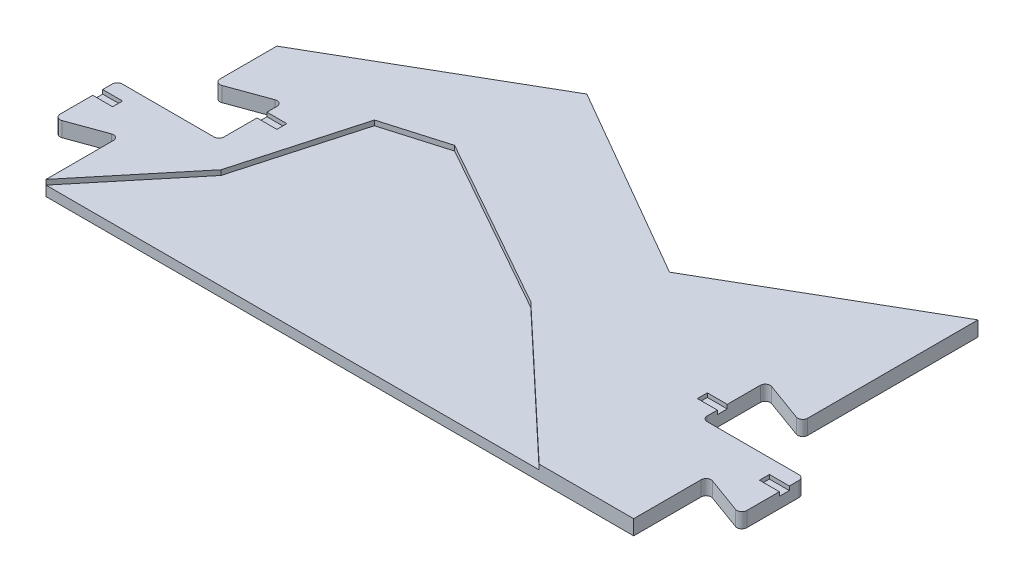
SolidWorks part; units mm, degrees
ref_plane "Přední rovina" through (0, 0, 0) normal (0, 0, 1) x (1, 0, 0)
ref_plane "Horní rovina" through (0, 0, 0) normal (0, 1, 0) x (1, 0, 0)
ref_plane "Pravá rovina" through (0, 0, 0) normal (1, 0, 0) x (0, 0, -1)
sketch "Skica1" plane through (0, 0, 0) normal (0, 1, 0) x (1, 0, 0)
  line L0 (-118.1438, 0) -> (-118.1438, 15)
  line L1 (-118.1438, 15) -> (-128.0938, 11.3785)
  line L2 (-128.0938, 11.3785) -> (-128.0938, 24.2785)
  line L3 (-107.6438, 24.2785) -> (-107.6438, 37.3785)
  line L4 (-107.6438, 37.3785) -> (-118.1432, 33.557)
  line L5 (-118.1432, 33.557) -> (-118.1432, 46.4149)
  line L6 (-118.1432, 46.4149) -> (-78.6351, 69.2249)
  line L7 (-78.6351, 69.2249) -> (-39.3176, 46.5249)
  line L8 (-118.1438, 15) -> (-118.1438, 58.9257) construction
  line L9 (-107.6438, 24.2785) -> (-128.0938, 24.2785)
  line L10 (-118.1438, 0) -> (-102.2271, 19.2785)
  line L11 (-102.2271, 19.2785) -> (-95.473, 43.3489)
  line L12 (-95.473, 43.3489) -> (-82.9972, 47.0032)
  line L13 (-82.9972, 47.0032) -> (-48.113, 27.4305)
  line L14 (-39.3176, 46.5249) -> (0, 69.2249)
  line L15 (-118.1438, 0) -> (0, 0)
  line L16 (-48.113, 27.4305) -> (-19, 0)
  line L17 (0, 0) -> (0, 15)
  line L18 (0, 69.2249) -> (0, 0) construction
  line L19 (-10.5, 24.2783) -> (9.9505, 24.2783)
  line L20 (0, 69.2249) -> (0, 33.5566)
  line L21 (0, 15) -> (9.9505, 11.3783)
  line L22 (9.9505, 24.2783) -> (9.9505, 11.3783)
  line L23 (0, 33.5566) -> (-10.5, 37.3783)
  line L24 (-10.5, 37.3783) -> (-10.5, 24.2783)
  point P23 (-0.2747, 24.2783)
  dimension "D1" = 45.4
  dimension "D2" = 45.62
  dimension "D3" = 120
  dimension "D4" = 70
  dimension "D5" = 12.9
  dimension "D6" = 13.1
  dimension "D7" = 15
  dimension "D8" = 69.2249
  dimension "D9" = 69.2249
  dimension "D10" = 25
  dimension "D11" = 25
  dimension "D12" = 13
  dimension "D13" = 40
  dimension "D14" = 45.4
  dimension "D15" = 120
  dimension "D16" = 118.1438
  dimension "D17" = 40
  dimension "D18" = 122
  dimension "D19" = 15
  dimension "D20" = 70
  dimension "D21" = 70
  dimension "D22" = 5
  dimension "D23" = 120
  dimension "D24" = 19
  dimension "D25" = 166
  dimension "D26" = 10.5
  dimension "D27" = 12.9
  dimension "D28" = 13.1
  dimension "D29" = 10.5
  dimension "D30" = 70
  dimension "D31" = 9.95
extrude "Přidat vysunutím1" add sketch "Skica1" along normal blind 3 contours L24 L23 L20 L14 L7 L6 L5 L4 L3 L9 L2 L1 L0 L10 L11 L12 L13 L16 L15 L17 L21 L22 L19 region at (-50.0339, 0, -36.1877)
extrude "Přidat vysunutím2" add sketch "Skica1<3>" along normal blind 2 contours L16 L13 L12 L11 L10 L15 region at (-72.3465, 0, -17.3507)
sketch "Skica1<3>" plane through (0, 0, 0) normal (0, 1, 0) x (1, 0, 0) same geometry as "Skica1"
fillet "Zaoblit3" radius 1 12 edges at (-107.6438, 1.5, -24.2785) (0, 1.5, -15) (9.9505, 1.5, -11.3783) (9.9505, 1.5, -24.2783) (-10.5, 1.5, -24.2783) (-10.5, 1.5, -37.3783) (0, 1.5, -33.5566) (-118.1438, 1.5, -15) (-128.0938, 1.5, -11.3785) (-128.0938, 1.5, -24.2785) (-107.6438, 1.5, -37.3785) (-118.1432, 1.5, -33.557)
sketch "Skica2" plane through (0, 3, 0) normal (0, 1, 0) x (1, 0, 0)
  line L0 (-107.6438, 30.6144) -> (-99.0463, 30.6144) construction
  line L1 (-107.6438, 25.2785) -> (-107.6438, 35.9503) construction
  line L7 (-102.2271, 19.2785) -> (-95.473, 43.3489) construction
  line L8 (-107.6438, 31.9144) -> (-103.6438, 31.9144)
  line L14 (-103.6438, 31.9144) -> (-103.6438, 33.9144)
  line L15 (-103.6438, 33.9144) -> (-107.6438, 33.9144)
  line L16 (-107.6438, 31.9144) -> (-107.6438, 33.9144)
  line L18 (-128.0938, 18.0426) -> (-119.4963, 18.0426) construction
  line L19 (-128.0938, 19.3426) -> (-124.0938, 19.3426)
  line L20 (-124.0938, 19.3426) -> (-124.0938, 21.3426)
  line L21 (-124.0938, 21.3426) -> (-128.0938, 21.3426)
  line L22 (-128.0938, 19.3426) -> (-128.0938, 21.3426)
  line L23 (-128.0938, 12.8066) -> (-128.0938, 23.2785) construction
  point P16 (-128.0938, 18.0426)
  point P17 (0, 0)
  dimension "D1" = 2
  dimension "D2" = 4
  dimension "D3" = 1.3
  dimension "D4" = 2
  dimension "D5" = 4
  dimension "D6" = 1.3
extrude "Odebrat vysunutím1" cut sketch "Skica2" against normal blind 0.8
sketch "Skica3" plane through (0, 3, 0) normal (0, 1, 0) x (1, 0, 0)
  line L0 (-10.5, 30.6142) -> (-49.1857, 30.6142) construction
  line L4 (-14.5, 27.3142) -> (-14.5, 29.3142)
  line L5 (-14.5, 29.3142) -> (-10.5, 29.3142)
  line L6 (-10.5, 27.3142) -> (-14.5, 27.3142)
  line L8 (-10.5, 29.3142) -> (-10.5, 27.3142)
  line L9 (-10.5, 35.9502) -> (-10.5, 25.2783) construction
  line L10 (9.9505, 18.0424) -> (-21.6052, 18.0424) construction
  line L15 (9.9505, 23.2783) -> (9.9505, 12.8065) construction
  line L16 (9.9505, 21.3424) -> (5.9505, 21.3424)
  line L17 (9.9505, 19.3424) -> (9.9505, 21.3424)
  line L18 (5.9505, 19.3424) -> (9.9505, 19.3424)
  line L19 (5.9505, 21.3424) -> (5.9505, 19.3424)
  point P10 (-10.5, 30.6142)
  point P15 (9.9505, 18.0424)
  point P16 (9.9505, 18.0424)
  point P17 (0, 0)
  point P20 (0, 0)
  dimension "D1" = 4
  dimension "D2" = 2
  dimension "D3" = 1.3
  dimension "D4" = 4
  dimension "D5" = 2
  dimension "D6" = 1.3
extrude "Odebrat vysunutím2" cut sketch "Skica3" against normal blind 0.8
